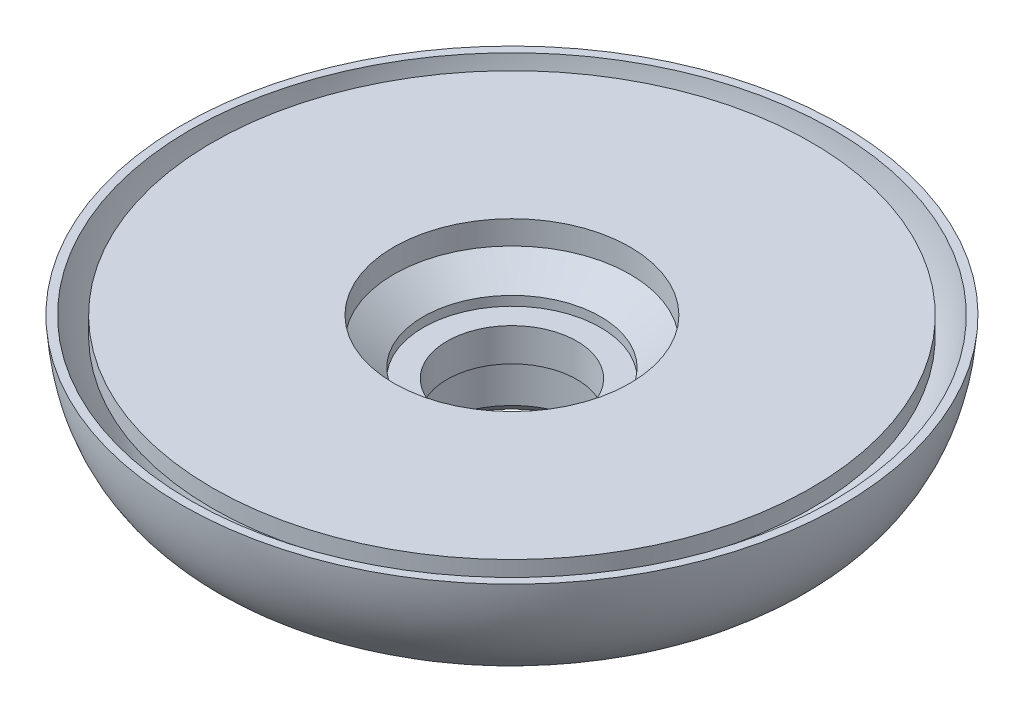
SolidWorks part; units mm, degrees
ref_plane "Front Plane" through (0, 0, 0) normal (0, 0, 1) x (1, 0, 0)
ref_plane "Top Plane" through (0, 0, 0) normal (0, 1, 0) x (1, 0, 0)
ref_plane "Right Plane" through (0, 0, 0) normal (1, 0, 0) x (0, 0, -1)
ref_axis "Axis1" through (-33.0333, 0, 0) along (1, 0, 0)
ref_axis "Axis2" through (0, 24.5224, 0) along (0, -1, 0)
ref_axis "Axis3" through (0, 0, -30.7663) along (0, 0, 1)
sketch "Sketch1" plane through (0, 0, 0) normal (0, 0, 1) x (1, 0, 0)
  line L5 (-21.8, 5.2071) -> (-8.6, 5.2071)
  line L6 (-8.6, 5.2071) -> (-8.6, 3.4877)
  line L7 (-8.6, 3.4877) -> (-6.45, 1.8932)
  line L8 (-6.45, 1.8932) -> (-6.45, 1.2071)
  line L9 (-6.45, 1.2071) -> (-4.725, 1.2071)
  line L10 (-4.725, 1.2071) -> (-4.725, -1.2071)
  line L11 (-4.725, -1.2071) -> (-5.7922, -1.2071)
  line L14 (-7.0393, -5.6929) -> (-8.0094, -5.6929)
  line L17 (-7.4842, -4.5126) -> (-13.4915, -4.5126)
  line L18 (-21.8, 5.2071) -> (-21.8, 3.9071)
  line L19 (-21.8, 3.9071) -> (-11, 3.9071)
  line L20 (-11, 3.9071) -> (-11, -3.9126)
  line L21 (-12.6169, -3.9126) -> (-11, -3.9126)
  line L22 (-4.725, 0) -> (0, 0) construction
  line L23 (-5.7922, -1.2071) -> (-5.7922, -4.5857)
  line L24 (-5.7922, -4.5857) -> (-7.0393, -5.6929)
  line L25 (-8.0094, -5.6929) -> (-8.0094, -4.9223)
  line L26 (-8.0094, -4.9223) -> (-7.4842, -4.5126)
  line L27 (-24, 5.2071) -> (-23.4, 5.2071)
  spline S0 degree 2 poles (-12.6169, -3.9126) (-22.0849, -3.9181) (-23.4, 5.2071) knots 0 0 0 1 1 1
  spline S1 degree 2 poles (-24, 5.2071) (-23.3621, -4.252) (-13.4915, -4.5126) knots 0 0 0 1 1 1
  point P16 (0, 0)
  dimension "D2" = 8.6
  dimension "D1" = 4.725
  dimension "D3" = 21.8
  dimension "D4" = 6.45
  dimension "D5" = 10.9
  dimension "D6" = 4
  dimension "D7" = 1.3
  dimension "D8" = 11
  dimension "D9" = 24
  dimension "D10" = 0.6
  dimension "D11" = 0.6
revolve "Revolve1" add sketch "Sketch1" angle 360 about axis through (0, 24.5224, 0) along (0, -1, 0)
